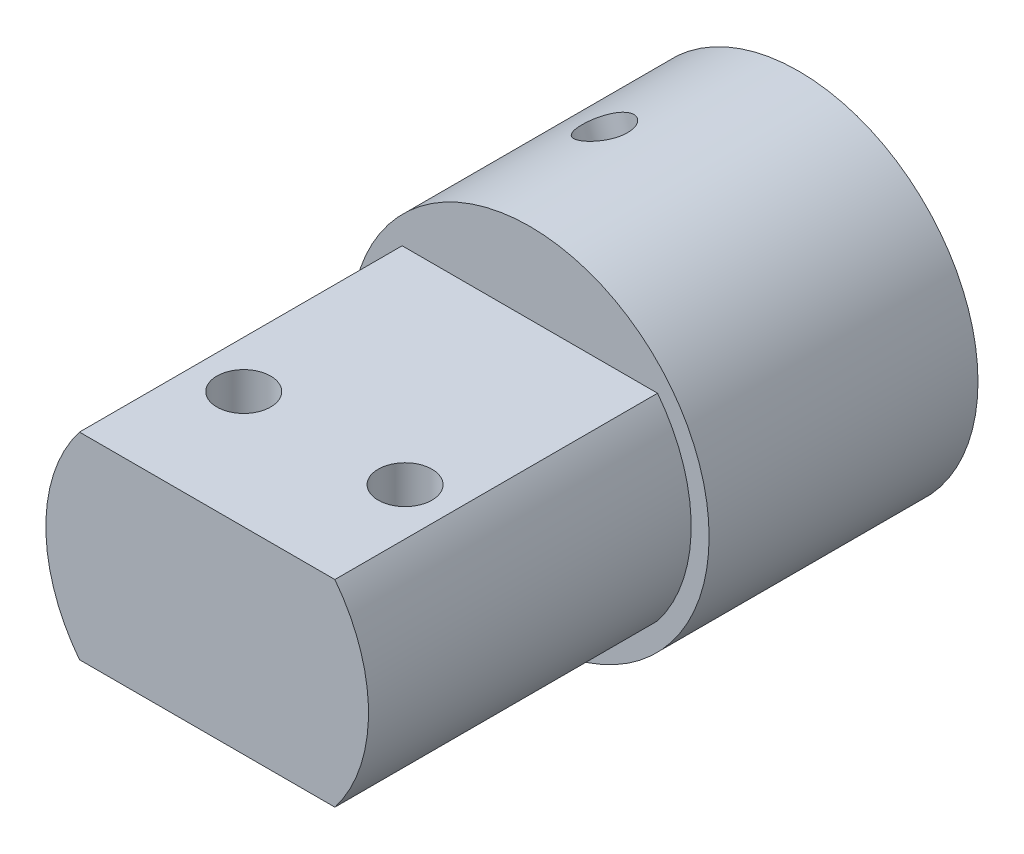
SolidWorks part; units mm, degrees
ref_plane "前视基准面" through (0, 0, 0) normal (0, 0, 1) x (1, 0, 0)
ref_plane "上视基准面" through (0, 0, 0) normal (0, 1, 0) x (1, 0, 0)
ref_plane "右视基准面" through (0, 0, 0) normal (1, 0, 0) x (0, 0, -1)
sketch "草图1" plane through (0, 0, 0) normal (0, 0, 1) x (1, 0, 0)
  line L0 (-11.4891, -8) -> (11.4891, -8)
  arc A0 (11.4891, -8) -> (-11.4891, -8) centre (0, 0) ccw
  circle A1 centre (0, 0) radius 5.25
  dimension "D1" = 28
  dimension "D3" = 10.5
  dimension "D2" = 8
extrude "凸台-拉伸1" add sketch "草图1" along normal blind 15
sketch "草图2" plane through (0, 0, 15) normal (0, 0, 1) x (1, 0, 0)
  line L0 (-13.4164, 4) -> (13.4164, 4)
  line L1 (-11.4891, -8) -> (11.4891, -8) construction
  arc A0 (11.4891, -8) -> (-11.4891, -8) centre (0, 0) ccw construction
  arc A1 (13.4164, 4) -> (-13.4164, 4) centre (0, 0) ccw
  dimension "D1" = 12
extrude "切除-拉伸1" cut sketch "草图2" against normal blind 10
sketch "草图3" plane through (0, 0, 15) normal (0, 0, 1) x (1, 0, 0)
  line L0 (-13.4164, 4) -> (-3.4004, 4) construction
  line L1 (-13.4164, 4) -> (-3.4004, 4) construction
  line L2 (-7.1239, 5.5) -> (7.1239, 5.5)
  line L3 (-7.1239, -5.5) -> (7.1239, -5.5)
  line L4 (-16.2067, 0) -> (21.8127, 0) construction
  line L6 (-16.2067, 5.5) -> (21.8127, 5.5) construction
  line L7 (-16.2067, -5.5) -> (21.8127, -5.5) construction
  arc A0 (-7.1239, 5.5) -> (-7.1239, -5.5) centre (0, 0) ccw
  arc A1 (7.1239, -5.5) -> (7.1239, 5.5) centre (0, 0) ccw
  dimension "D4" = 18
  dimension "D1" = 1.5
  dimension "D2" = 11
  dimension "D3" = 5.5
extrude "凸台-拉伸2" add sketch "草图3" along normal blind 18
sketch "草图4" plane through (0, 5.5, 0) normal (0, 1, 0) x (1, 0, 0)
  line L0 (0, 10.497) -> (0, -50.4006) construction
  line L1 (7.1239, -33) -> (-7.1239, -33) construction
  circle A0 centre (4.5, -26.46) radius 1.5
  circle A1 centre (-4.5, -26.46) radius 1.5
  dimension "D1" = 3
  dimension "D2" = 4.5
  dimension "D3" = 6.54
extrude "切除-拉伸2" cut sketch "草图4" against normal through all
sketch "草图5" plane through (0, 0, 0) normal (0, 0, -1) x (-1, 0, 0)
  circle A0 centre (0, 0) radius 5.25
  circle A1 centre (0, 0) radius 14
extrude "凸台-拉伸3" add sketch "草图5" against normal blind 15
sketch "草图6" plane through (0, 0, 0) normal (0, 0, -1) x (-1, 0, 0)
  circle A0 centre (0, 0) radius 10
  circle A1 centre (0, 0) radius 18.0436
  dimension "D1" = 20
extrude "切除-拉伸3" cut sketch "草图6" against normal blind 15
sketch "草图7" plane through (0, 0, 0) normal (0, 0, -1) x (-1, 0, 0)
  line L0 (-1.5084, 4.7671) -> (4.154, 2.7828)
  line L2 (4.154, 2.7828) -> (-1.5084, 4.7671) construction
  arc A0 (-1.5084, 4.7671) -> (4.154, 2.7828) centre (0, 0) ccw
  circle A1 centre (0, 0) radius 6.9865
  dimension "D1" = 10
  dimension "D2" = 0
extrude "凸台-拉伸4" add sketch "草图7" against normal blind 15
sketch "草图8" plane through (-1.3228, 3.7749, 0) normal (0.3307, -0.9437, 0) x (0.9437, 0.3307, 0)
  circle A0 centre (0, 7.5443) radius 1.35
  dimension "D1" = 2.7
extrude "切除-拉伸4" cut sketch "草图8" against normal blind 15
